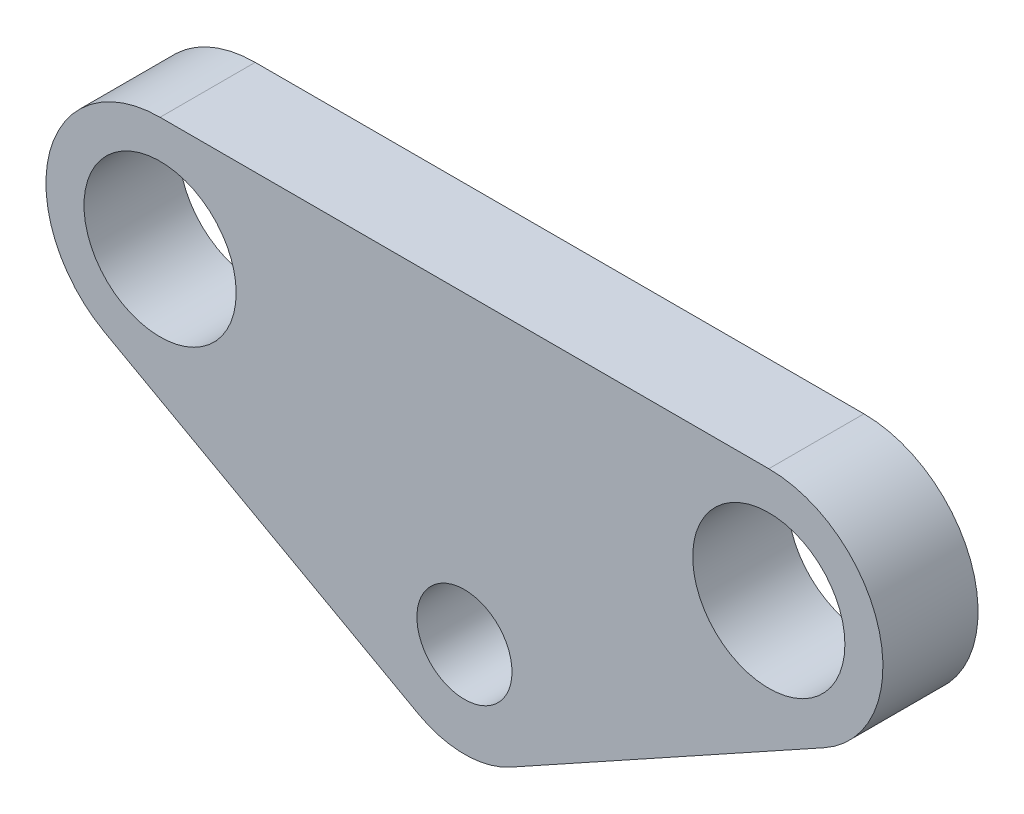
SolidWorks part; units mm, degrees
ref_plane "Front Plane" through (0, 0, 0) normal (0, 0, 1) x (1, 0, 0)
ref_plane "Top Plane" through (0, 0, 0) normal (0, 1, 0) x (1, 0, 0)
ref_plane "Right Plane" through (0, 0, 0) normal (1, 0, 0) x (0, 0, -1)
sketch "Sketch1" plane through (0, 0, 0) normal (0, 0, 1) x (1, 0, 0)
  line L0 (-16, 16) -> (16, 16)
  line L1 (0, 0) -> (0, 18.7938) construction
  line L11 (18.9059, 4.7506) -> (2.4216, -4.3745)
  line L12 (-18.9059, 4.7506) -> (-2.4216, -4.3745)
  circle A0 centre (0, 0) radius 11.5 construction
  circle A1 centre (-16, 10) radius 11.5 construction
  circle A2 centre (16, 10) radius 11.5 construction
  circle A3 centre (-16, 10) radius 4
  arc A5 (-18.9059, 4.7506) -> (-16, 16) centre (-16, 10) cw
  circle A6 centre (16, 10) radius 4
  arc A7 (18.9059, 4.7506) -> (16, 16) centre (16, 10) ccw
  circle A8 centre (0, 0) radius 2.5
  circle A9 centre (0, 0) radius 5 construction
  arc A10 (-2.4216, -4.3745) -> (2.6999, -4.2084) centre (0, 0) ccw
  point P21 (0, -12)
  dimension "D1" = 23
  dimension "D3" = 8
  dimension "D4" = 6
  dimension "D7" = 10
  dimension "D5" = 5
  dimension "D6" = 10
  dimension "D2" = 16
extrude "Boss-Extrude1" add sketch "Sketch1" along normal blind 5 contours A7 A5 A6 A3 region at (0, 7.5067, 0)
